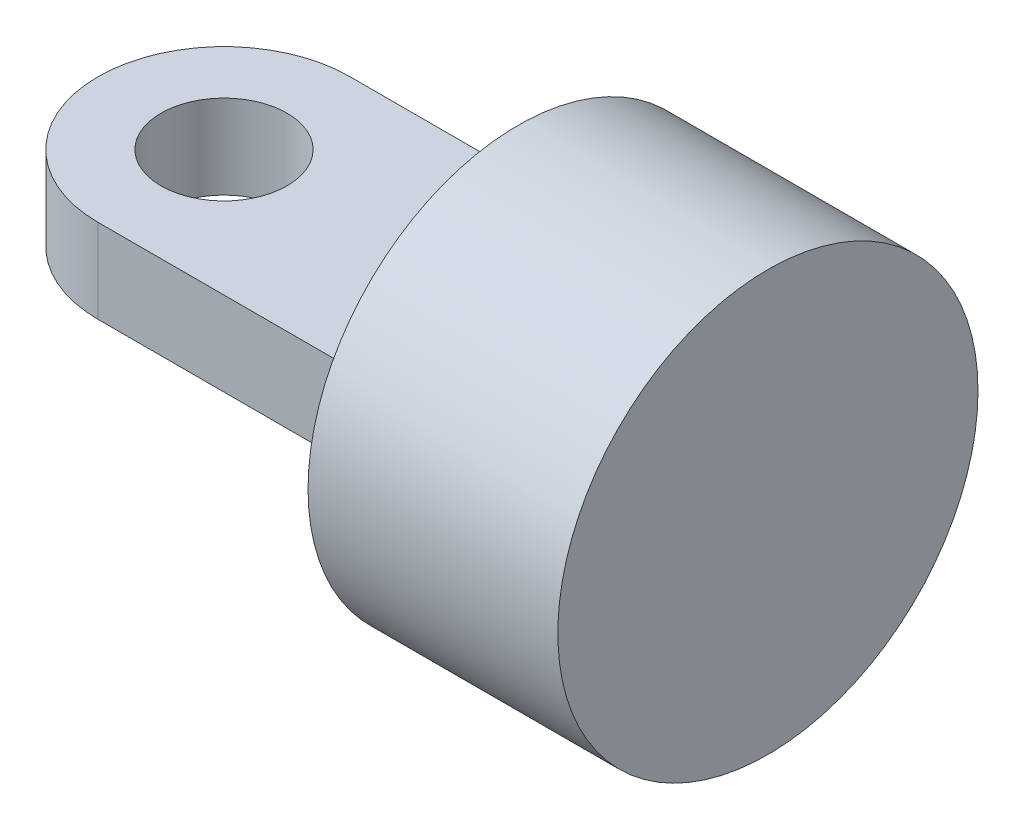
SolidWorks part; units mm, degrees
ref_plane "Front Plane" through (0, 0, 0) normal (0, 0, 1) x (1, 0, 0)
ref_plane "Top Plane" through (0, 0, 0) normal (0, 1, 0) x (1, 0, 0)
ref_plane "Right Plane" through (0, 0, 0) normal (1, 0, 0) x (0, 0, -1)
sketch "Sketch1" plane through (0, 0, 0) normal (1, 0, 0) x (0, 0, -1)
  circle A0 centre (0, 0) radius 50
extrude "Boss-Extrude1" add sketch "Sketch1" against normal blind 129.45
sketch "Sketch2" plane through (0, 0, 0) normal (0, 1, 0) x (1, 0, 0)
  line L0 (-129.45, 50) -> (-129.45, -50) construction
  line L1 (-129.45, 30) -> (-59.45, 30)
  line L2 (-59.45, 30) -> (-59.45, -30)
  line L3 (-59.45, -30) -> (-129.45, -30)
  circle A0 centre (-129.45, 0) radius 15
  arc A1 (-129.45, 30) -> (-129.45, -30) centre (-129.45, 0) ccw
  dimension "D1" = 70
sketch "Sketch3" plane through (0, 0, 0) normal (0, 1, 0) x (1, 0, 0)
  line L0 (-129.45, 50) -> (-129.45, -50) construction
  line L1 (-132.7526, 53.2141) -> (-59.45, 53.2141)
  line L2 (-132.7526, 53.2141) -> (-132.7526, -59.4456)
  line L3 (-132.7526, -59.4456) -> (-59.45, -59.4456)
  line L4 (-59.45, 53.2141) -> (-59.45, -59.4456)
  dimension "D1" = 70
extrude "Cut-Extrude1" cut sketch "Sketch3" against normal blind 129.45 and the other way blind 129.45
extrude "Boss-Extrude2" add sketch "Sketch2" along normal blind 10 and the other way blind 10
